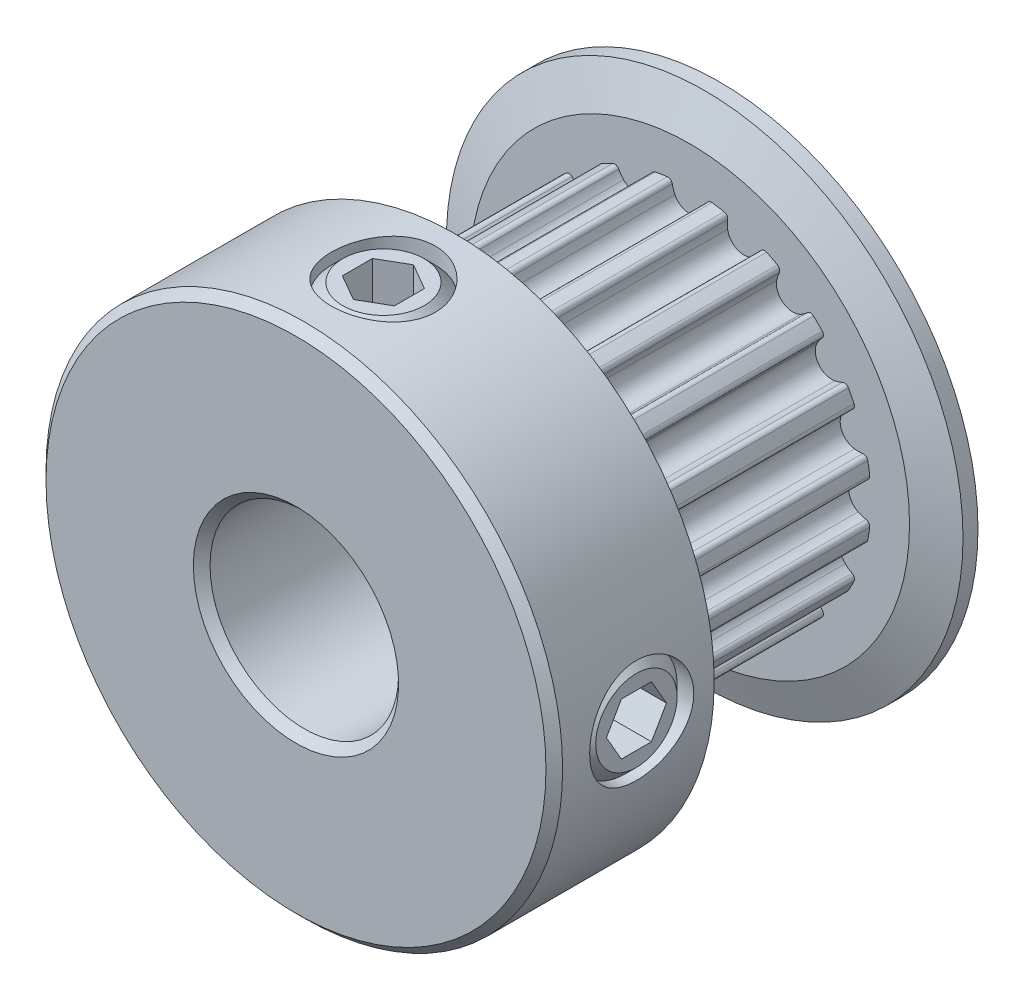
SolidWorks part; units mm, degrees
ref_plane "Front Plane" through (0, 0, 0) normal (0, 0, 1) x (1, 0, 0)
ref_plane "Top Plane" through (0, 0, 0) normal (0, 1, 0) x (1, 0, 0)
ref_plane "Right Plane" through (0, 0, 0) normal (1, 0, 0) x (0, 0, -1)
sketch "Sketch1" plane through (0, 0, 0) normal (0, 0, 1) x (1, 0, 0)
  line L1 (-1.7499, 5.3585) -> (1.7499, 5.3585) construction
  line L4 (0, 0) -> (0, 5.3585) construction
  line L5 (0, 5.3585) -> (0, 11.1054) construction
  line L6 (0, 6.3625) -> (1.9751, 6.0482) construction
  line L7 (1.9751, 6.0482) -> (2.6648, 5.8229) construction
  line L8 (1.9751, 6.0482) -> (1.7499, 5.3585) construction
  line L9 (-1.9751, 6.0482) -> (-1.7499, 5.3585) construction
  line L10 (-1.8963, 5.8067) -> (-2.841, 8.6995)
  line L11 (-2.841, 8.6995) -> (2.841, 8.6995)
  line L12 (2.841, 8.6995) -> (1.8963, 5.8067)
  circle A0 centre (0, 0) radius 6.3625 construction
  circle A1 centre (0, 0) radius 8.6995 construction
  circle A2 centre (0, 0) radius 6.1085 construction
  arc A3 (-0.4989, 5.6703) -> (0.4989, 5.6703) centre (0, 5.9135) ccw
  arc A4 (-0.4989, 5.6703) -> (-0.5855, 5.9387) centre (0.4, 6.1085) cw
  arc A5 (-1.8963, 5.8067) -> (-0.7518, 6.0621) centre (0, 0) cw
  arc A6 (-0.5855, 5.9387) -> (-0.7518, 6.0621) centre (-0.7333, 5.9132) ccw
  arc A7 (1.8963, 5.8067) -> (0.7518, 6.0621) centre (0, 0) ccw
  arc A8 (0.5855, 5.9387) -> (0.7518, 6.0621) centre (0.7333, 5.9132) cw
  arc A9 (0.4989, 5.6703) -> (0.5855, 5.9387) centre (-0.4, 6.1085) ccw
  point P6 (0, 20.9083)
  point P11 (0, 6.3625)
  point P13 (0, 8.6995)
  point P14 (0, 6.1085)
  dimension "D1" = 9.803
  dimension "D2" = 4.7429
sketch "Sketch2" plane through (0, 0, 0) normal (1, 0, 0) x (0, 0, -1)
  line L0 (-7.135, 3.175) -> (7.135, 3.175)
  line L1 (-7.135, 3.175) -> (-7.135, 8.6995)
  line L2 (-1.75, 8.6995) -> (-7.135, 8.6995)
  line L3 (-2.255, 3.175) -> (-2.255, 8.6995) construction
  line L4 (-2.255, 8.6995) -> (-1.245, 8.6995) construction
  line L5 (-1.245, 8.6995) -> (-1.245, 6.1085) construction
  line L6 (-1.245, 6.1085) -> (6.125, 6.1085)
  line L7 (6.125, 6.1085) -> (6.125, 8.6995) construction
  line L8 (6.125, 8.6995) -> (7.135, 8.6995) construction
  line L9 (7.135, 8.6995) -> (7.135, 3.175)
  line L10 (-7.135, 0) -> (7.135, 0) construction
  line L11 (6.63, 8.6995) -> (6.125, 7.404)
  line L12 (-1.245, 7.404) -> (-1.75, 8.6995)
  line L14 (-1.245, 7.404) -> (-1.245, 6.1085)
  line L15 (6.125, 6.1085) -> (6.125, 7.404)
  line L16 (6.63, 8.6995) -> (7.135, 8.6995)
  arc A0 (-1.245, 7.404) -> (-1.75, 8.6995) centre (-3.1592, 7.404) ccw construction
  arc A1 (6.125, 7.404) -> (6.63, 8.6995) centre (8.0392, 7.404) cw construction
  point P12 (-1.245, 7.404)
  point P14 (-1.75, 8.6995)
  point P20 (6.125, 7.404)
  point P21 (6.63, 8.6995)
  point P25 (6.125, 0)
  point P26 (-1.245, 0)
  dimension "OA" = 14.27
  dimension "Bore" = 6.35
  dimension "Outside Width" = 8.38
  dimension "Inside Width" = 7.37
revolve "Revolve1" add sketch "Sketch2" angle 360 mid plane about L10
sketch "Sketch3" plane through (0, 0, 0) normal (0, 0, 1) x (1, 0, 0)
  line L6 (2.841, 8.6995) -> (-2.841, 8.6995)
  line L7 (1.8963, 5.8067) -> (2.841, 8.6995)
  line L8 (-2.841, 8.6995) -> (-1.8963, 5.8067)
  line L9 (2.841, 8.6995) -> (-2.841, 8.6995)
  line L10 (1.8963, 5.8067) -> (2.841, 8.6995)
  line L11 (-2.841, 8.6995) -> (-1.8963, 5.8067)
  arc A8 (1.8963, 5.8067) -> (0.7518, 6.0621) centre (0, 0) ccw
  arc A9 (0.7518, 6.0621) -> (0.5855, 5.9387) centre (0.7333, 5.9132) ccw
  arc A10 (0.4989, 5.6703) -> (0.5855, 5.9387) centre (-0.4, 6.1085) ccw
  arc A11 (-0.4989, 5.6703) -> (0.4989, 5.6703) centre (0, 5.9135) ccw
  arc A12 (-0.5855, 5.9387) -> (-0.4989, 5.6703) centre (0.4, 6.1085) ccw
  arc A13 (-0.5855, 5.9387) -> (-0.7518, 6.0621) centre (-0.7333, 5.9132) ccw
  arc A14 (-0.7518, 6.0621) -> (-1.8963, 5.8067) centre (0, 0) ccw
  arc A15 (1.8963, 5.8067) -> (0.7518, 6.0621) centre (0, 0) ccw
  arc A16 (0.7518, 6.0621) -> (0.5855, 5.9387) centre (0.7333, 5.9132) ccw
  arc A17 (0.4989, 5.6703) -> (0.5855, 5.9387) centre (-0.4, 6.1085) ccw
  arc A18 (-0.4989, 5.6703) -> (0.4989, 5.6703) centre (0, 5.9135) ccw
  arc A19 (-0.5855, 5.9387) -> (-0.4989, 5.6703) centre (0.4, 6.1085) ccw
  arc A20 (-0.5855, 5.9387) -> (-0.7518, 6.0621) centre (-0.7333, 5.9132) ccw
  arc A21 (-0.7518, 6.0621) -> (-1.8963, 5.8067) centre (0, 0) ccw
  dimension "D1" = 0
extrude "Cut-Extrude1" cut sketch "Sketch3" against normal up to vertex (6.125 mm away) from vertex up to point (0, 6.1085, -6.125) starting at point (0, 6.1085, 1.245)
pattern_circular "CirPattern1" count 20 over 360 about axis through (0, 0, 7.135) along (0, 0, 1) of "Cut-Extrude1"
sketch "Sketch4" plane through (0, 0, 0) normal (1, 0, 0) x (0, -1, 0)
  line L0 (0, -1.245) -> (0, -7.135) construction
  line L1 (-3.175, -7.135) -> (3.175, -7.135) construction
  line L2 (7.404, -1.245) -> (-7.404, -1.245) construction
  circle A0 centre (0, -4.19) radius 1.7526
extrude "Cut-Extrude2" cut sketch "Sketch4" along normal through all
ref_plane "Plane1" through (0, 0, 4.19) normal (0, 0, 1) x (1, 0, 0)
sketch "Sketch5" plane through (0, 0, 4.19) normal (0, 0, 1) x (1, 0, 0)
  line L0 (0, 0) -> (0, 8.6995) construction
  line L1 (3.175, -1.3716) -> (3.175, 0)
  line L2 (3.556, -1.7526) -> (8.1401, -1.7526)
  line L3 (3.175, 0) -> (8.6995, 0) construction
  line L4 (3.175, 0) -> (8.5211, 0)
  line L5 (8.5211, 0) -> (8.5211, -1.3716)
  line L6 (3.556, -1.7526) -> (3.175, -1.3716)
  line L7 (8.5211, -1.3716) -> (8.1401, -1.7526)
  circle A0 centre (0, 0) radius 8.6995 construction
  circle A1 centre (0, 0) radius 3.175 construction
  point P2 (3.175, -1.7526)
  point P11 (8.5211, -1.7526)
revolve "Revolve2" add sketch "Sketch5" angle 360 mid plane about L4
sketch "Sketch6" plane through (8.5211, 5.3841, 0) normal (-1, 0, 0) x (0, -1, 0)
  line L1 (5.3841, 5.2019) -> (4.5078, 4.6959)
  line L2 (4.5078, 4.6959) -> (4.5078, 3.6841)
  line L3 (4.5078, 3.6841) -> (5.3841, 3.1781)
  line L4 (5.3841, 3.1781) -> (6.2604, 3.6841)
  line L5 (6.2604, 3.6841) -> (6.2604, 4.6959)
  line L6 (6.2604, 4.6959) -> (5.3841, 5.2019)
  circle A0 centre (5.3841, 4.19) radius 0.8763 construction
  dimension "D1" = 1.7526
extrude "Cut-Extrude3" cut sketch "Sketch6" along normal blind 1.3144
pattern_circular "CirPattern3" count 2 over 90 about axis through (0, 0, 7.135) along (0, 0, 1) of "Cut-Extrude2", "Revolve2", "Cut-Extrude3"
chamfer "Chamfer1" distance 0.2807 angle 45 2 edges at (3.175, 0, 7.135) (8.6995, 0, 7.135)
ref_axis "Center Axis 1" through (0, 0, -7.135) along (0, 0, 1)
ref_plane "Contact Plane 1" through (0, 0, 7.135) normal (0, 0, 1) x (1, 0, 0)
ref_plane "Contact Plane 2" through (0, 0, -7.135) normal (0, 0, -1) x (-1, 0, 0)
equation "\"D2@Sketch1\"= \"D1@Sketch1\" / 2"
equation "\"D1@Sketch6\" = \"Set Screw@Sketch4\" / 2"
equation "\"D1@Cut-Extrude3\" = \"D1@Sketch6\"*.75"
